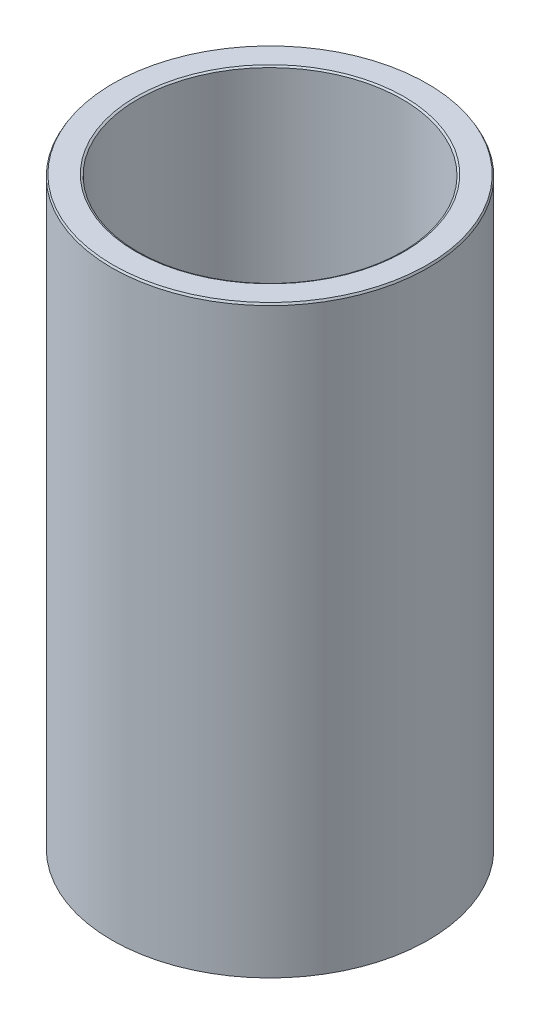
SolidWorks part; units mm, degrees
ref_plane "Front Plane" through (0, 0, 0) normal (0, 0, 1) x (1, 0, 0)
ref_plane "Top Plane" through (0, 0, 0) normal (0, 1, 0) x (1, 0, 0)
ref_plane "Right Plane" through (0, 0, 0) normal (1, 0, 0) x (0, 0, -1)
sketch "Sketch1" plane through (0, 0, 0) normal (0, 1, 0) x (1, 0, 0)
  circle A0 centre (0, 0) radius 50
  dimension "SLEEVE_OD" = 100
extrude "Boss-Extrude1" add sketch "Sketch1" along normal blind 184.9401
sketch "Sketch2" plane through (0, 0, 0) normal (0, 1, 0) x (1, 0, 0)
  circle A0 centre (0, 0) radius 41.7769
  dimension "BORE_D" = 83.5538
extrude "Cut-Extrude1" cut sketch "Sketch2" along normal through all
chamfer "Chamfer1" distance 0.616 angle 30 4 edges at (0, 184.9401, 41.7769) (0, 0, 41.7769) (0, 0, 50) (0, 184.9401, 50) first distance on face at (0, 184.9401, 41.7769) first distance on face at (0, 0, 41.7769) first distance on face at (0, 184.9401, 50)
